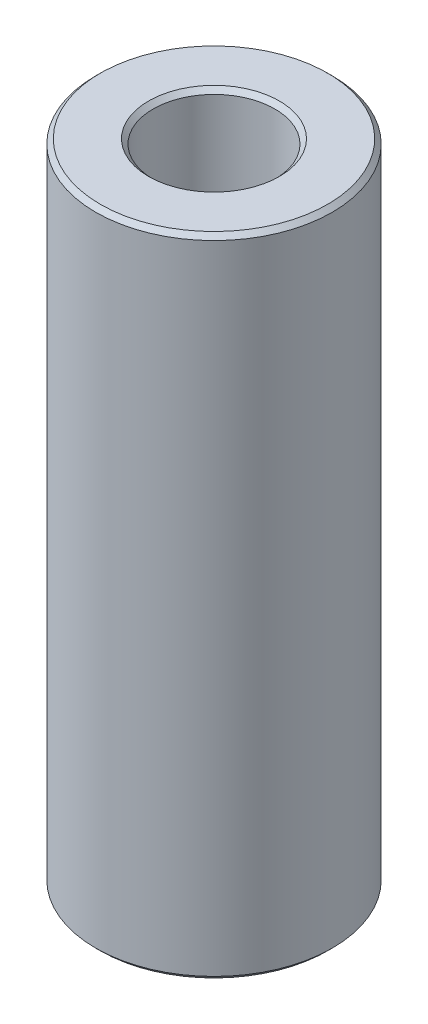
SolidWorks part; units mm, degrees
ref_plane "Front Plane" through (0, 0, 0) normal (0, 0, 1) x (1, 0, 0)
ref_plane "Top Plane" through (0, 0, 0) normal (0, 1, 0) x (1, 0, 0)
ref_plane "Right Plane" through (0, 0, 0) normal (1, 0, 0) x (0, 0, -1)
sketch "Sketch1" plane through (0, 0, 0) normal (0, 1, 0) x (1, 0, 0)
  circle A0 centre (0, 0) radius 25
  dimension "SLEEVE_OD" = 50
extrude "Boss-Extrude1" add sketch "Sketch1" along normal blind 136.6758
sketch "Sketch2" plane through (0, 0, 0) normal (0, 1, 0) x (1, 0, 0)
  circle A0 centre (0, 0) radius 12.8607
  dimension "BORE_D" = 25.7214
extrude "Cut-Extrude1" cut sketch "Sketch2" along normal through all
chamfer "Chamfer1" distance 0.9721 angle 45 4 edges at (0, 136.6758, 12.8607) (0, 0, 12.8607) (0, 0, 25) (0, 136.6758, 25)
